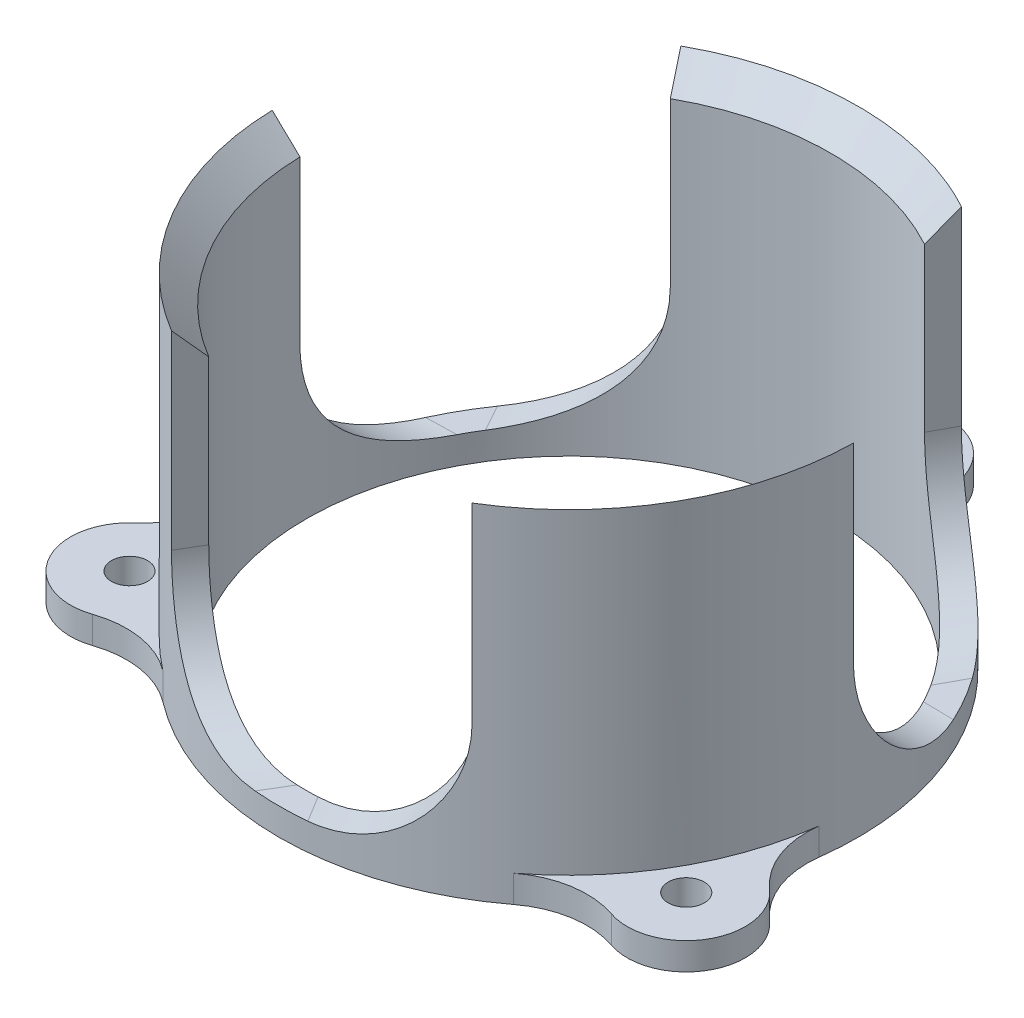
SolidWorks part; units mm, degrees
ref_plane "Front Plane" through (0, 0, 0) normal (0, 0, 1) x (1, 0, 0)
ref_plane "Top Plane" through (0, 0, 0) normal (0, 1, 0) x (1, 0, 0)
ref_plane "Right Plane" through (0, 0, 0) normal (1, 0, 0) x (0, 0, -1)
sketch "Sketch1" plane through (0, 0, 0) normal (0, 1, 0) x (1, 0, 0)
  line L0 (0, 0) -> (0, 35.5313) construction
  circle A0 centre (0, 0) radius 29
  arc A1 (-12.3553, 29.5186) -> (-31.7415, -4.0593) centre (0, 0) ccw
  circle A2 centre (0, 35.5313) radius 2
  arc A3 (6.4069, 36.8003) -> (-6.4069, 36.8003) centre (0, 35.5313) ccw
  arc A4 (-12.3553, 29.5186) -> (-6.4069, 36.8003) centre (-16.2163, 38.7431) ccw
  arc A5 (12.3553, 29.5186) -> (6.4069, 36.8003) centre (16.2163, 38.7431) cw
  circle A6 centre (30.7711, -17.7657) radius 2
  arc A7 (19.3862, -25.4593) -> (28.6665, -23.9487) centre (25.4444, -33.4153) cw
  arc A8 (28.6665, -23.9487) -> (35.0734, -12.8516) centre (30.7711, -17.7657) ccw
  arc A9 (31.7415, -4.0593) -> (35.0734, -12.8516) centre (41.6607, -5.3278) ccw
  circle A10 centre (-30.7711, -17.7657) radius 2
  arc A11 (-31.7415, -4.0593) -> (-35.0734, -12.8516) centre (-41.6607, -5.3278) cw
  arc A12 (-35.0734, -12.8516) -> (-28.6665, -23.9487) centre (-30.7711, -17.7657) ccw
  arc A13 (-19.3862, -25.4593) -> (-28.6665, -23.9487) centre (-25.4444, -33.4153) ccw
  arc A14 (-19.3862, -25.4593) -> (19.3862, -25.4593) centre (0, 0) ccw
  arc A15 (31.7415, -4.0593) -> (12.3553, 29.5186) centre (0, 0) ccw
  point P29 (0, 0)
  dimension "D1" = 58
  dimension "D2" = 3
  dimension "D3" = 10
  dimension "D4" = 10
  dimension "D5" = 3
extrude "Boss-Extrude1" add sketch "Sketch1" along normal blind 3
sketch "Sketch2" plane through (0, 3, 0) normal (0, 1, 0) x (1, 0, 0)
  line L0 (0, 0) -> (0, 32) construction
  line L1 (-15.5566, 27.9641) -> (-14.0982, 25.3425)
  line L2 (-28.9916, -0.6996) -> (-31.9907, -0.7719)
  line L3 (-28.9916, -0.6996) -> (-14.0982, 25.3425) construction
  line L4 (31.9959, -0.5096) -> (28.9963, -0.4619)
  line L5 (13.89, 25.4572) -> (15.3268, 28.0907)
  line L6 (-16.4393, -27.4545) -> (-14.8981, -24.8806)
  line L7 (15.1016, -24.7577) -> (16.6638, -27.3188)
  arc A0 (-28.9916, -0.6996) -> (-14.8981, -24.8806) centre (0, 0) ccw
  arc A1 (-31.9907, -0.7719) -> (-16.4393, -27.4545) centre (0, 0) ccw
  arc A2 (-12.3553, 29.5186) -> (-31.7415, -4.0593) centre (0, 0) ccw construction
  arc A4 (13.89, 25.4572) -> (-14.0982, 25.3425) centre (0, 0) ccw
  arc A5 (15.3268, 28.0907) -> (-15.5566, 27.9641) centre (0, 0) ccw
  arc A6 (15.1016, -24.7577) -> (28.9963, -0.4619) centre (0, 0) ccw
  arc A7 (16.6638, -27.3188) -> (31.9959, -0.5096) centre (0, 0) ccw
  point P24 (0, 0)
  dimension "D1" = 30
  dimension "D2" = 3
extrude "Boss-Extrude2" add sketch "Sketch2" along normal blind 35
fillet "Fillet1" radius 14 6 edges at (30.4961, 3, 0.4857) (15.8827, 3, 26.0382) (-15.6687, 3, 26.1676) (-30.4911, 3, 0.7357) (-14.8274, 3, -26.6533) (14.6084, 3, -26.774)
chamfer "Chamfer1" distance 3 angle 45 3 edges at (-0.1189, 38, -28.9998) (25.174, 38, 14.3969) (-25.0551, 38, 14.6028)
